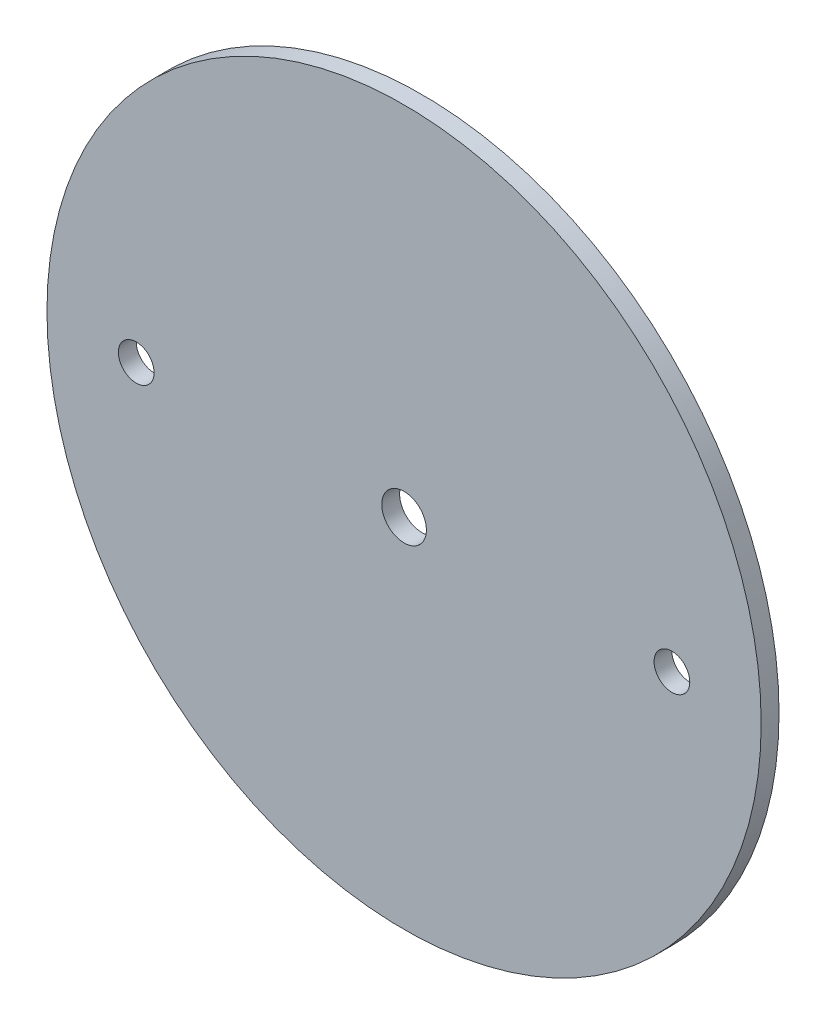
SolidWorks part; units mm, degrees
ref_plane "Front Plane" through (0, 0, 0) normal (0, 0, 1) x (1, 0, 0)
ref_plane "Top Plane" through (0, 0, 0) normal (0, 1, 0) x (1, 0, 0)
ref_plane "Right Plane" through (0, 0, 0) normal (1, 0, 0) x (0, 0, -1)
sketch "Sketch1" plane through (0, 0, 0) normal (0, 0, 1) x (1, 0, 0)
  circle A0 centre (0, 0) radius 63.5
extrude "Boss-Extrude1" add sketch "Sketch1" along normal mid plane 3.175
sketch "Sketch2" plane through (0, 0, 1.5875) normal (0, 0, 1) x (1, 0, 0)
  line L0 (-1000, 0) -> (49000, 0) construction
  line L1 (0, -1000) -> (0, 49000) construction
  point P4 (47.625, 0)
  point P5 (-47.625, 0)
  dimension "D2" = 95.25
  dimension "D1" = 47.625
hole_wizard "1/4 (0.25) Diameter Hole1" positions "Sketch2" profile "Sketch3" hole size "1/4" standard "ANSI Inch" end condition through all
sketch "Sketch3" plane through (-47.625, 0, 1.5875) normal (1, 0, 0) x (0, -1, 0)
  line L0 (0, 0) -> (0, 3.175)
  line L1 (0, 3.175) -> (3.175, 3.175)
  line L2 (3.175, 3.175) -> (3.175, 0)
  line L5 (3.175, 0) -> (0, 0)
  line L11 (0, -6.35) -> (0, 107.95) construction
  dimension "Thru Hole Dia." = 6.35
  dimension "Thru Hole Depth" = 3.175
sketch "Sketch4" plane through (0, 0, 1.5875) normal (0, 0, 1) x (1, 0, 0)
  point P0 (0, 0)
hole_wizard "5/16 (0.3125) Diameter Hole1" positions "Sketch4" profile "Sketch5" hole size "5/16" standard "ANSI Inch"
sketch "Sketch5" plane through (0, 0, 1.5875) normal (1, 0, 0) x (0, -1, 0)
  line L0 (0, 0) -> (0, 3.302)
  line L1 (0, 3.302) -> (3.9687, 3.302)
  line L2 (3.9687, 3.302) -> (3.9688, 0)
  line L5 (3.9688, 0) -> (0, 0)
  line L10 (0, 3.302) -> (-3.9688, 3.302) construction
  line L11 (0, -6.35) -> (0, 107.95) construction
  dimension "Hole Dia." = 7.9375
  dimension "Hole Depth" = 3.302
  dimension "Drill Angle" = 180
equation "\"AIRFRAME_OD\"= 5.15in"
equation "\"AIRFRAME_ID\"= 5.00in"
equation "\"FLAT_T\"= 0.125in"
equation "\"NOSE_EXP_L\"= 27in"
equation "\"NOSE_SHOULDER_L\"= 5in"
equation "\"MAIN_L\"= 30in"
equation "\"RECO_COUP_L\"= 10in"
equation "\"RECO_SWITCH_L\"= 2in"
equation "\"DROGUE_L\"= 20in"
equation "\"ATS_FORE_COUP_L\"= 5.5in"
equation "\"ATS_AFT_COUP_L\"= 4.5in"
equation "\"LOWER_L\"= 30in"
equation "\"FIN_N\"= 4"
equation "\"CR_AFT_X\"= 0.5in"
equation "\"CR_FORE_X\"= 9.25in"
equation "\"FIN_ROOT\"= 8in"
equation "\"FIN_X\"= 0.75in"
equation "\"MOTOR_OD\"= 3.091in"
equation "\"MOTOR_ID\"= 3.00in"
equation "\"COUPLER_OD\"= 4.998in"
equation "\"COUPLER_ID\"= 4.88in"
equation "\"D1@Sketch1\"=\"AIRFRAME_ID\""
equation "\"D1@Boss-Extrude1\"=\"FLAT_T\""
equation "\"RECO_ROD_X\"= 3.5in"
equation "\"ATS_ROD_X\"= 3.75in"
equation "\"D2@Sketch2\"=\"ATS_ROD_X\""
equation "\"MOTOR_L\"= 14in"
equation "\"MOTOR_LOWER_X\"= 2in"
equation "\"D1@Sketch2\"=\"ATS_ROD_X\"/2"
